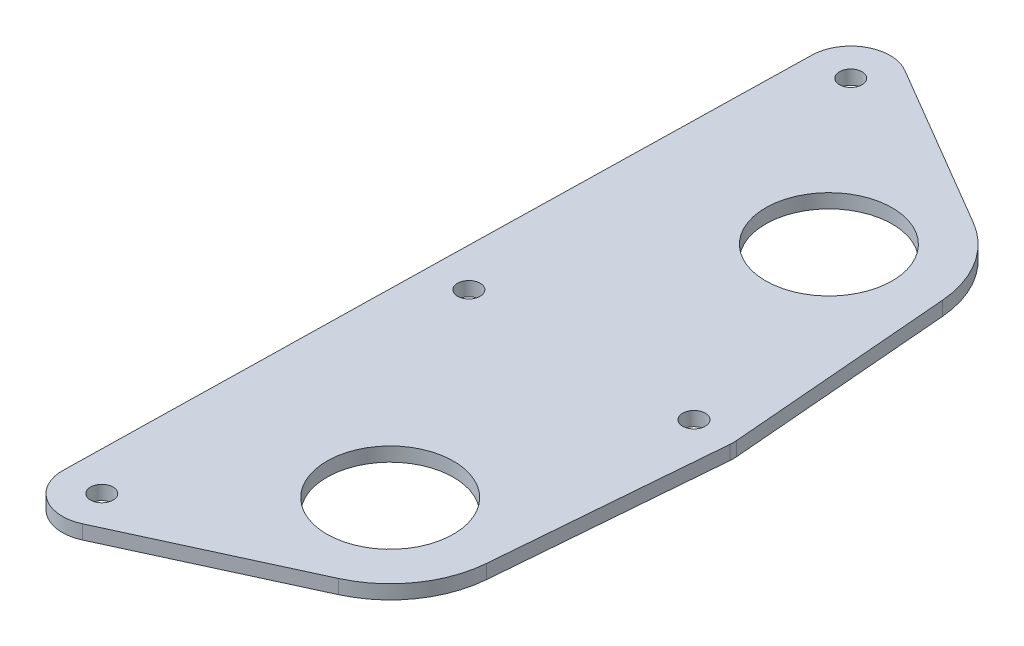
SolidWorks part; units mm, degrees
material "6061-T6 (SS)"
ref_plane "Front" through (0, 0, 0) normal (0, 0, 1) x (1, 0, 0)
ref_plane "Top" through (0, 0, 0) normal (0, 1, 0) x (1, 0, 0)
ref_plane "Right" through (0, 0, 0) normal (1, 0, 0) x (0, 0, -1)
sketch "Sketch1" plane through (0, 0, 0) normal (0, 1, 0) x (1, 0, 0)
  line L0 (0, 49.5046) -> (0, -49.5046) construction
  line L4 (-50.8, 95.25) -> (38.1, 95.25)
  line L5 (-50.8, 95.25) -> (-50.8, -95.25)
  line L6 (-50.8, -95.25) -> (38.1, -95.25)
  line L7 (38.1, 95.25) -> (38.1, -95.25)
  circle A0 centre (0, 49.5046) radius 14.2875
  circle A1 centre (0, -49.5046) radius 14.2875
  circle A4 centre (0, 49.5046) radius 38.1 construction
  circle A5 centre (0, -49.5046) radius 38.1 construction
  point P4 (0, 0)
  point P12 (38.1, 0)
  dimension "D2" = 28.575
  dimension "D3" = 50.8
  dimension "D4" = 76.2
  dimension "D1" = 99.0092
  dimension "D5" = 190.5
extrude "Boss-Extrude1" add sketch "Sketch1" along normal blind 3.175
hole_wizard "#10 Clearance Hole1" positions "Sketch2" profile "Sketch3" hole size "#10" standard "ANSI Inch"
sketch "Sketch2" plane through (0, 3.175, 0) normal (0, 1, 0) x (1, 0, 0)
  line L6 (0, 49.5046) -> (0, -49.5046) construction
  circle A0 centre (0, 49.5046) radius 46.0375 construction
  circle A1 centre (0, -49.5046) radius 46.0375 construction
  circle A3 centre (0, 49.5046) radius 38.1 construction
  circle A5 centre (0, -49.5046) radius 14.2875 construction
  circle A6 centre (0, 49.5046) radius 14.2875 construction
  point P2 (19.05, 0)
  point P4 (-29.9949, 84.4296)
  point P10 (-33.3375, -81.2546)
  point P40 (-31.75, 0)
  point P67 (-34.925, -77.6566)
  point P68 (-32.97, -81.6361)
  dimension "D3" = 7.9375
  dimension "D4" = 31.75
  dimension "D1" = 19.05
  dimension "D2" = 31.75
  dimension "D5" = 34.925
sketch "Sketch3" plane through (19.05, 3.175, 0) normal (1, 0, 0) x (0, 0, 1)
  line L0 (0, 0) -> (0, 4.7088)
  line L1 (0, 4.7088) -> (2.5527, 3.175)
  line L2 (2.5527, 3.175) -> (2.5527, 0)
  line L5 (2.5527, 0) -> (0, 0)
  line L10 (0, 4.7088) -> (-2.5527, 3.175) construction
  line L11 (0, -6.35) -> (0, 107.95) construction
  dimension "Hole Dia." = 5.1054
  dimension "Hole Depth" = 3.175
  dimension "Drill Angle" = 118
sketch "Sketch4" plane through (0, 3.175, 0) normal (0, 1, 0) x (1, 0, 0)
  line L0 (12.0665, 70.0335) -> (-25.4837, 92.1047)
  line L1 (-38.8957, 84.6146) -> (-40.6509, 0.1795)
  line L2 (-42.2385, -81.0807) -> (-40.6509, 0.1795)
  line L3 (-29.6165, -89.3424) -> (9.9528, -71.1374)
  line L4 (23.7317, 51.465) -> (27.9225, 0.7329)
  line L5 (23.7317, -51.465) -> (27.9225, -0.7329)
  circle A0 centre (0, 49.5046) radius 23.8125 construction
  circle A1 centre (-29.9949, 84.4296) radius 8.9027 construction
  circle A2 centre (-31.75, 0) radius 8.9027 construction
  circle A3 centre (19.05, 0) radius 8.9027 construction
  circle A4 centre (-33.3375, -81.2546) radius 8.9027 construction
  circle A5 centre (0, -49.5046) radius 23.8125 construction
  circle A6 centre (-29.9949, 84.4296) radius 2.5527 construction
  circle A7 centre (0, 49.5046) radius 14.2875 construction
  arc A8 (12.0665, 70.0335) -> (23.7317, 51.465) centre (0, 49.5046) cw
  arc A9 (-38.8957, 84.6146) -> (-25.4837, 92.1047) centre (-29.9949, 84.4296) cw
  arc A10 (-29.6165, -89.3424) -> (-42.2385, -81.0807) centre (-33.3375, -81.2546) cw
  arc A11 (9.9528, -71.1374) -> (23.7317, -51.465) centre (0, -49.5046) ccw
  arc A14 (27.9225, -0.7329) -> (27.9225, 0.7329) centre (19.05, 0) ccw
  point P33 (0, 0)
  dimension "D1" = 6.35
  dimension "D2" = 9.525
extrude "Cut-Extrude1" cut sketch "Sketch4" against normal through all flip side to cut
